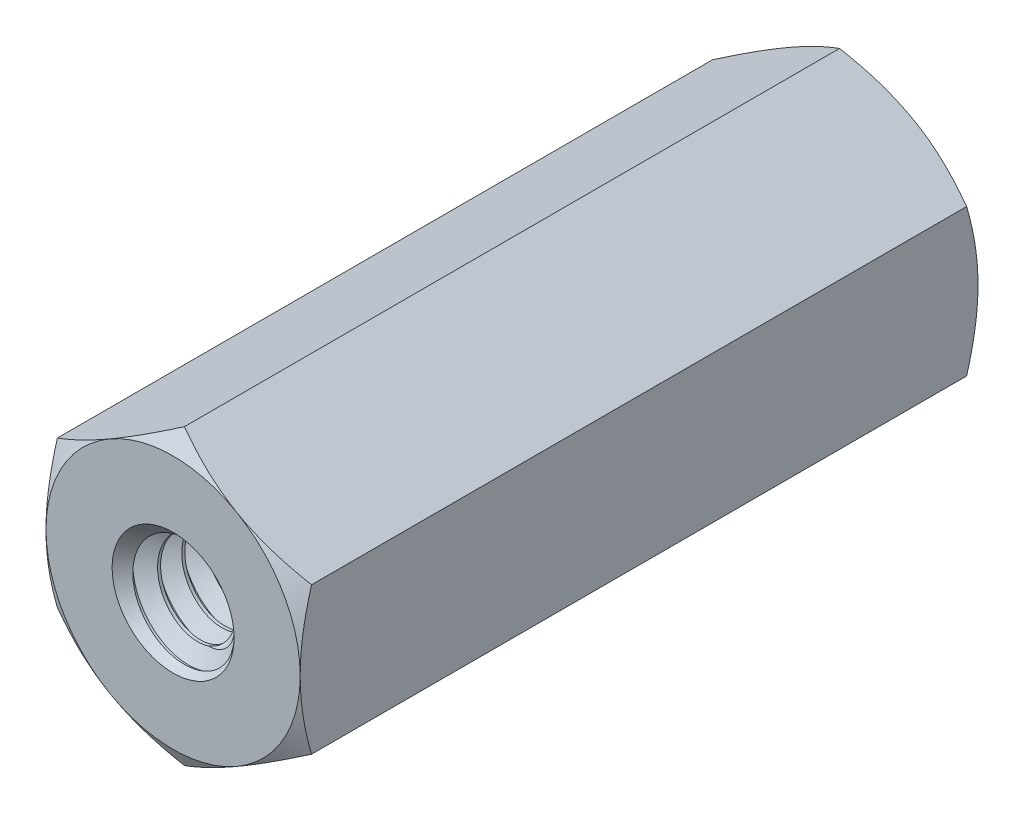
SolidWorks part; units mm, degrees
ref_plane "Front Plane" through (0, 0, 0) normal (0, 0, 1) x (1, 0, 0)
ref_plane "Top Plane" through (0, 0, 0) normal (0, 1, 0) x (1, 0, 0)
ref_plane "Right Plane" through (0, 0, 0) normal (1, 0, 0) x (0, 0, -1)
sketch "Sketch3" plane through (0, 0, 0) normal (1, 0, 0) x (0, 0, -1)
  line L0 (-6.35, 0) -> (6.35, 0) construction
  line L1 (0, 2.3813) -> (0, -2.3813) construction
  line L2 (-6.35, 1.0922) -> (-6.35, -1.0922) construction
  point P2 (-6.35, 0)
  point P3 (6.35, 0)
  dimension "Length" = 12.7
  dimension "Min Thread Length" = 12.7
  dimension "D1" = 12.7
  dimension "Thread Dia" = 2.1844
  dimension "Hex" = 4.7625
sketch "Sketch1" plane through (0, 0, 0) normal (0, 0, 1) x (1, 0, 0)
  line L1 (0, 2.7496) -> (-2.3813, 1.3748)
  line L2 (-2.3813, 1.3748) -> (-2.3813, -1.3748)
  line L3 (-2.3813, -1.3748) -> (0, -2.7496)
  line L4 (0, -2.7496) -> (2.3812, -1.3748)
  line L5 (2.3812, -1.3748) -> (2.3812, 1.3748)
  line L6 (2.3812, 1.3748) -> (0, 2.7496)
  circle A0 centre (0, 0) radius 2.3813 construction
  circle A1 centre (0, 0) radius 1.0922
extrude "Extrude1" add sketch "Sketch1" along normal up to vertex (6.35 mm away) and the other way up to vertex (6.35 mm away) up to point (0, 0, 6.35) other way up to point (0, 0, -6.35)
sketch "Sketch11" plane through (0, 0, -6.35) normal (0, 0, -1) x (-1, 0, 0)
  circle A0 centre (0, 0) radius 1.0922 construction
  circle A1 centre (0, 0) radius 1.0922
curve "Helix/Spiral1" pitch 0.4536 height 13.1536 turns 29 parameters "Pitch"=0.4536
sketch "Sketch12" plane through (0, 0, 0) normal (1, 0, 0) x (0, 0, -1)
  line L0 (6.7469, 1.0922) -> (6.35, 1.0922)
  line L1 (6.7469, 1.0922) -> (6.5768, 0.7976)
  line L2 (6.5768, 0.7976) -> (6.5201, 0.7976)
  line L3 (6.5201, 0.7976) -> (6.35, 1.0922)
  line L4 (6.5484, 0.7976) -> (6.5484, 1.0922) construction
  line L5 (6.6618, 0.9449) -> (6.435, 0.9449) construction
  dimension "D1" = 0.0567
  dimension "D2" = 0.2268
  dimension "D3" = 60
sweep "Sweep1" add profiles "Sketch12" path "Helix/Spiral1"
sketch "Sketch6" plane through (0, 0, -6.35) normal (0, 0, -1) x (-1, 0, 0)
  line L6 (0, 2.7496) -> (-2.3812, 1.3748)
  line L7 (-2.3812, 1.3748) -> (-2.3812, -1.3748)
  line L8 (-2.3812, -1.3748) -> (0, -2.7496)
  line L9 (0, -2.7496) -> (2.3813, -1.3748)
  line L10 (2.3813, -1.3748) -> (2.3813, 1.3748)
  line L11 (2.3813, 1.3748) -> (0, 2.7496)
  line L12 (0, 2.7496) -> (-2.3812, 1.3748)
  line L13 (-2.3812, 1.3748) -> (-2.3812, -1.3748)
  line L14 (-2.3812, -1.3748) -> (0, -2.7496)
  line L15 (0, -2.7496) -> (2.3813, -1.3748)
  line L16 (2.3813, -1.3748) -> (2.3813, 1.3748)
  line L17 (2.3813, 1.3748) -> (0, 2.7496)
  dimension "D1" = 0
extrude "Extrude2" cut sketch "Sketch6" along normal through all
sketch "Sketch7" plane through (0, 0, -6.35) normal (0, 0, -1) x (-1, 0, 0)
  circle A2 centre (0, 0) radius 1.143
  circle A3 centre (0, 0) radius 1.143
  dimension "D1" = 0.0508
extrude "Extrude3" cut sketch "Sketch7" against normal through all draft 43
sketch "Sketch8" plane through (0, 0, -6.35) normal (0, 0, -1) x (-1, 0, 0)
  circle A0 centre (0, 0) radius 2.3813 construction
  circle A1 centre (0, 0) radius 2.3813
extrude "Extrude4" cut sketch "Sketch8" against normal through all draft 60 flip side to cut
mirror "Mirror1" about plane through (0, 0, 0) normal (0, 0, 1) of "Extrude2", "Extrude3", "Extrude4"
sketch "Sketch9" [suppressed] plane through (0, 0, 0) normal (1, 0, 0) x (0, 0, -1)
  line L1 (-12.7, 2.4638) -> (12.7, 2.4638)
  line L2 (-12.7, 2.4638) -> (-12.7, 0)
  line L3 (-12.7, 0) -> (12.7, 0)
  line L4 (12.7, 2.4638) -> (12.7, 0)
  line L7 (-25.4, 0) -> (25.4, 0) construction
revolve "Revolve" [suppressed] add sketch "Sketch9" angle 360 about L0
sketch "Sketch10" [suppressed] plane through (0, 0, 0) normal (1, 0, 0) x (0, 0, -1)
  line L0 (25.4, 2.413) -> (12.7, 2.413)
  line L1 (-25.4, 2.413) -> (-12.7, 2.413)
  line L2 (12.7, 2.413) -> (12.7, -2.413)
  line L3 (-25.4, -2.4638) -> (-12.7, -2.4638)
  line L4 (-12.7, 2.413) -> (-12.7, -2.4638)
  line L5 (12.7, -2.413) -> (25.4, -2.413)
equation "\"D1@Sketch3\" = \"Min Thread Length@Sketch3\""
equation "\"D3@Helix/Spiral1\" = \"Length@Sketch3\"+\"Pitch@Helix/Spiral1\""
equation "\"D1@Sketch12\" = \"Pitch@Helix/Spiral1\"*.125"
equation "\"D2@Sketch12\" = \"Pitch@Helix/Spiral1\"*.5"
